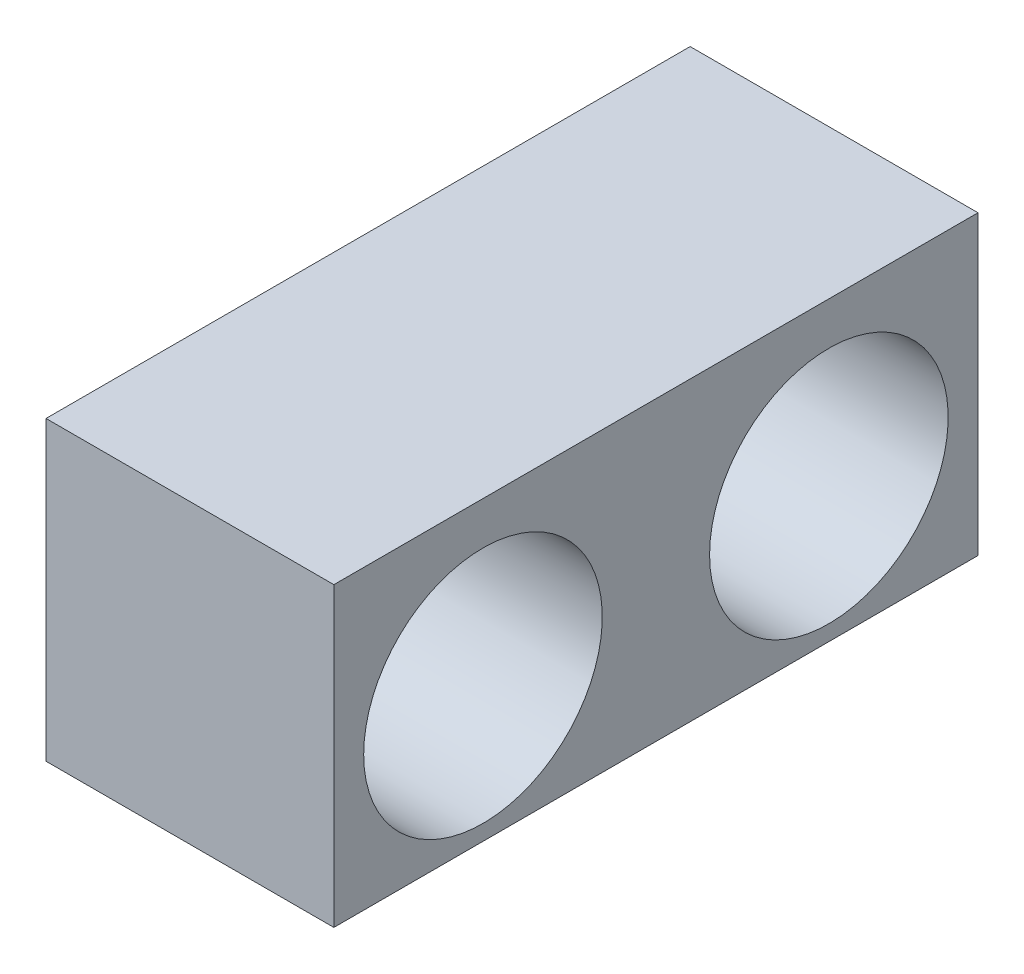
SolidWorks part; units mm, degrees
ref_plane "Front Plane" through (0, 0, 0) normal (0, 0, 1) x (1, 0, 0)
ref_plane "Top Plane" through (0, 0, 0) normal (0, 1, 0) x (1, 0, 0)
ref_plane "Right Plane" through (0, 0, 0) normal (1, 0, 0) x (0, 0, -1)
other "Lead Shot"
sketch "Sketch1" plane through (0, 0, 0) normal (0, 1, 0) x (1, 0, 0)
  circle A0 centre (0, 0) radius 75
  dimension "D1" = 150
extrude "Boss-Extrude1" add sketch "Sketch1" along normal blind 100
sketch "Sketch2" plane through (0, 100, 0) normal (0, 1, 0) x (1, 0, 0)
  line L1 (-22.2, -49.6757) -> (-22.2, 49.6757) construction
  line L3 (-22.2, -49.6757) -> (-22.2, 49.6757)
  line L4 (22.2, 49.6757) -> (22.2, -49.6757) construction
  line L5 (22.2, 49.6757) -> (22.2, -49.6757)
  line L6 (-22.2, -49.6757) -> (22.2, -49.6757)
  line L7 (-22.2, 49.6757) -> (22.2, 49.6757)
extrude "Cut-Extrude1" cut sketch "Sketch2" against normal through all flip side to cut
sketch "Sketch3" plane through (0, 0, 49.6757) normal (0, 0, 1) x (1, 0, 0)
  line L0 (-28.2, 45.7908) -> (-22.2, 45.7908) construction
  line L1 (-28.2, 45.7908) -> (-22.2, 45.7908) construction
  line L3 (-22.2, 45.7908) -> (22.2, 45.7908)
  line L4 (-22.2, 45.7908) -> (-22.2, 100)
  line L5 (-22.2, 100) -> (22.2, 100)
  line L6 (22.2, 45.7908) -> (22.2, 100)
extrude "Cut-Extrude2" cut sketch "Sketch3" against normal through all
sketch "Sketch4" plane through (-22.2, 0, 0) normal (-1, 0, 0) x (0, 0, 1)
  circle A0 centre (26.6757, 20.7908) radius 18.4 construction
  circle A1 centre (-26.6757, 20.7908) radius 18.4 construction
  circle A2 centre (26.6757, 20.7908) radius 18.4
  circle A3 centre (-26.6757, 20.7908) radius 18.4
extrude "Cut-Extrude3" cut sketch "Sketch4" against normal through all
